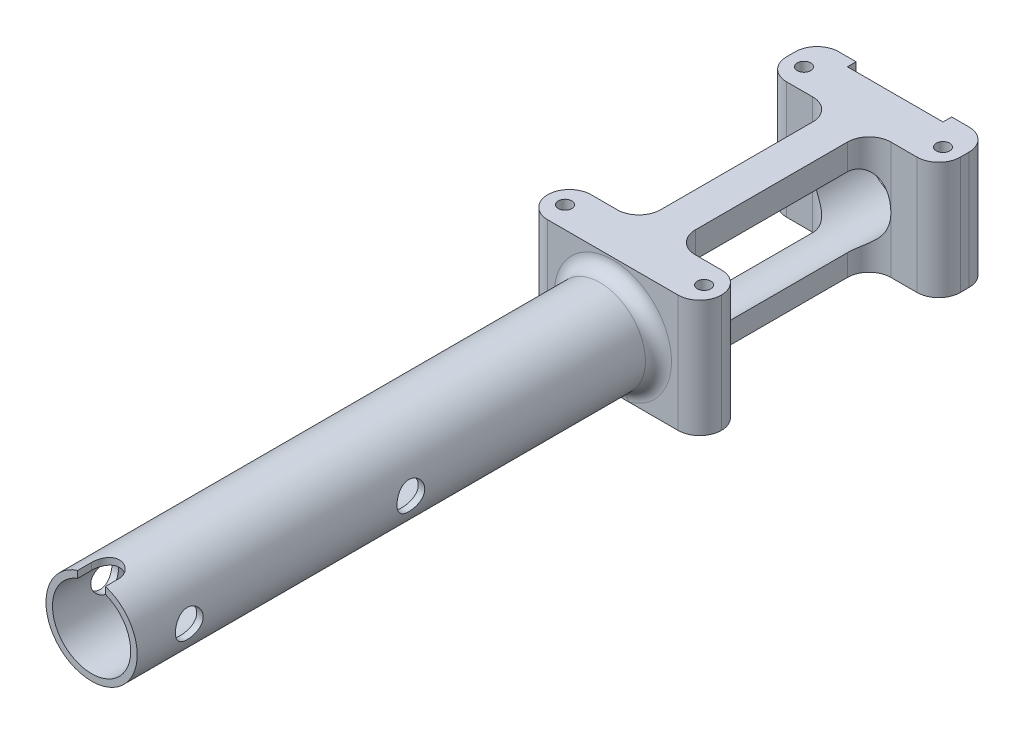
SolidWorks part; units mm, degrees
material "6063-T6"
ref_plane "Front Plane" through (0, 0, 0) normal (0, 0, 1) x (1, 0, 0)
ref_plane "Top Plane" through (0, 0, 0) normal (0, 1, 0) x (1, 0, 0)
ref_plane "Right Plane" through (0, 0, 0) normal (1, 0, 0) x (0, 0, -1)
sketch "Sketch1" plane through (0, 0, 0) normal (0, 0, 1) x (1, 0, 0)
  circle A1 centre (0, 0) radius 10.5
  dimension "D1" = 21
extrude "Boss-Extrude1" add sketch "Sketch1" along normal blind 120
sketch "Sketch3" plane through (0, 0, 0) normal (0, 1, 0) x (1, 0, 0)
  line L0 (0, 0) -> (0, 101.6874) construction
  line L1 (0, 0) -> (-109.3194, 0) construction
  line L2 (20, 0) -> (-20, 0)
  line L3 (-20, 0) -> (-20, 10)
  line L4 (-20, 10) -> (-4, 10)
  line L5 (-4, 10) -> (-4, 55)
  line L6 (-4, 55) -> (-20, 55)
  line L7 (-20, 55) -> (-20, 65)
  line L8 (-20, 65) -> (20, 65)
  line L9 (20, 55) -> (20, 65)
  line L10 (4, 55) -> (20, 55)
  line L11 (4, 10) -> (4, 55)
  line L12 (20, 10) -> (4, 10)
  line L13 (20, 0) -> (20, 10)
  line L14 (-20, 5) -> (36.7917, 5) construction
  line L15 (-20, 60) -> (26.8388, 60) construction
  line L16 (-16, 5) -> (-16, 60) construction
  circle A0 centre (-16, 5) radius 1.55
  circle A1 centre (16, 5) radius 1.55
  circle A4 centre (-16, 60) radius 1.55
  circle A5 centre (16, 60) radius 1.55
  point P12 (0, 65)
  dimension "D6" = 3.1
  dimension "D1" = 20
  dimension "D2" = 45
  dimension "D3" = 10
  dimension "D4" = 10
  dimension "D5" = 8
  dimension "D7" = 4
extrude "Boss-Extrude2" add sketch "Sketch3" along normal blind 14 and the other way blind 13
sketch "Sketch5" plane through (0, 0, -65) normal (0, 0, -1) x (-1, 0, 0)
  line L0 (0, 0) -> (0, 55.8767) construction
  line L1 (-20, 14) -> (-11, 14)
  line L2 (-20, 14) -> (20, 14) construction
  line L3 (-11, 14) -> (-11, -13)
  line L4 (-20, -13) -> (20, -13) construction
  line L5 (-11, -13) -> (-20, -13)
  line L6 (-20, -13) -> (-20, 14)
  line L7 (20, -13) -> (20, 14)
  line L8 (11, -13) -> (20, -13)
  line L9 (11, 14) -> (11, -13)
  line L10 (20, 14) -> (11, 14)
  circle A0 centre (0, 0) radius 10
  dimension "D1" = 20
  dimension "D2" = 11
extrude "Boss-Extrude3" add sketch "Sketch5" along normal blind 2
sketch "Sketch6" plane through (0, 0, 0) normal (0, 0, 1) x (1, 0, 0)
  circle A0 centre (0, 0) radius 9
  dimension "D1" = 18
extrude "Cut-Extrude1" cut sketch "Sketch6" against normal through all both and the other way through all
sketch "Sketch7" plane through (0, 0, 0) normal (1, 0, 0) x (0, 0, -1)
  line L0 (-120, 9) -> (-120, -9) construction
  circle A0 centre (-57, 0) radius 3.2
  circle A1 centre (-108, 0) radius 3.2
  dimension "D1" = 6.4
  dimension "D2" = 12
  dimension "D3" = 63
extrude "Cut-Extrude2" cut sketch "Sketch7" against normal through all both and the other way through all
sketch "Sketch8" plane through (0, 0, 0) normal (0, 1, 0) x (1, 0, 0)
  line L0 (0, 0) -> (0, -186.8535) construction
  line L1 (3.2, -120) -> (-3.2, -120)
  line L2 (-3.2, -120) -> (-3.2, -116.8)
  line L3 (3.2, -120) -> (3.2, -116.8)
  line L4 (-10.5, -120) -> (10.5, -120) construction
  arc A0 (-3.2, -116.8) -> (3.2, -116.8) centre (0, -116.8) cw
  point P9 (0, -120)
  dimension "D1" = 3.2
  dimension "D2" = 3.2
extrude "Cut-Extrude3" cut sketch "Sketch8" along normal through all
sketch "Sketch9" plane through (0, 0, 0) normal (0, 1, 0) x (1, 0, 0)
  line L0 (0, 0) -> (0, 130.9865) construction
  line L1 (0, 0) -> (-78.8906, 0) construction
  line L2 (-11, 0) -> (-11, 123.8815)
  line L3 (-11, 123.8815) -> (-26.9661, 123.8815)
  line L4 (-26.9661, 123.8815) -> (-26.9661, 0)
  line L5 (-26.9661, 0) -> (-11, 0)
  line L6 (-11, 67) -> (-11, 65) construction
  line L7 (26.9661, 0) -> (11, 0)
  line L8 (26.9661, 123.8815) -> (26.9661, 0)
  line L9 (11, 123.8815) -> (26.9661, 123.8815)
  line L10 (11, 0) -> (11, 123.8815)
extrude "Cut-Extrude5" [suppressed] cut sketch "Sketch9" against normal through all and the other way blind 9
fillet "Fillet1" radius 5 16 edges at (-4, 11.0311, -55) (4, 11.0311, -55) (-4, 11.0311, -10) (4, 11.0311, -10) (-4, -10.5311, -55) (4, -10.5311, -55) (4, -10.5311, -10) (-4, -10.5311, -10) (-20, 0.5, -10) (-20, 0.5, 0) (-20, 0.5, -55) (20, 0.5, -55) (20, 0.5, -10) (20, 0.5, 0) (-20, 0.5, -67) (20, 0.5, -67)
fillet "Fillet2" [suppressed] radius 2
fillet "Fillet3" radius 3 1 edges at (10.5, 0, 0)
